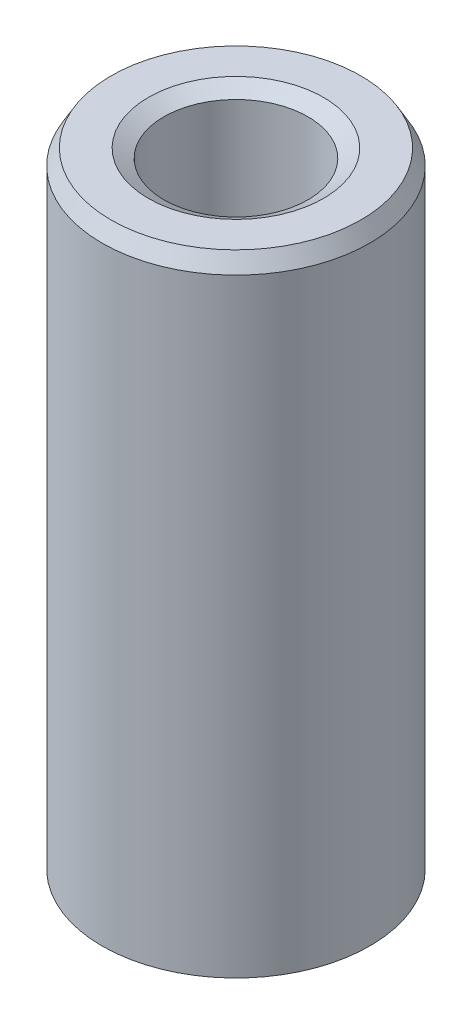
SolidWorks part; units mm, degrees
ref_plane "Front Plane" through (0, 0, 0) normal (0, 0, 1) x (1, 0, 0)
ref_plane "Top Plane" through (0, 0, 0) normal (0, 1, 0) x (1, 0, 0)
ref_plane "Right Plane" through (0, 0, 0) normal (1, 0, 0) x (0, 0, -1)
sketch "Sketch1" plane through (0, 0, 0) normal (0, 1, 0) x (1, 0, 0)
  circle A0 centre (0, 0) radius 30
  dimension "SLEEVE_OD" = 60
extrude "Boss-Extrude1" add sketch "Sketch1" along normal blind 141.9168
sketch "Sketch2" plane through (0, 0, 0) normal (0, 1, 0) x (1, 0, 0)
  circle A0 centre (0, 0) radius 16.1427
  dimension "BORE_D" = 32.2853
extrude "Cut-Extrude1" cut sketch "Sketch2" along normal through all
chamfer "Chamfer1" distance 3.4841 angle 30 4 edges at (0, 141.9168, 16.1427) (0, 0, 16.1427) (0, 0, 30) (0, 141.9168, 30) first distance on face at (0, 141.9168, 16.1427) first distance on face at (0, 0, 16.1427) first distance on face at (0, 141.9168, 30)
